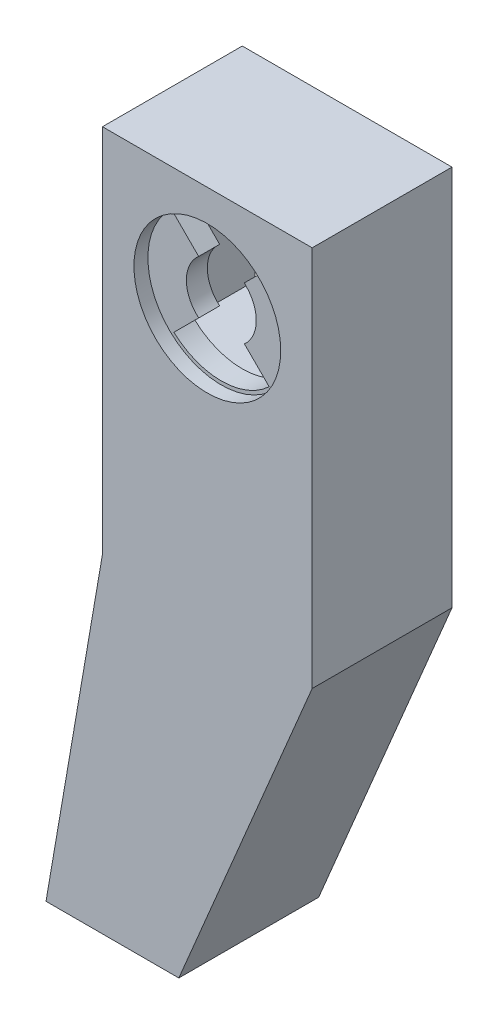
SolidWorks part; units mm, degrees
ref_plane "Front Plane" through (0, 0, 0) normal (0, 0, 1) x (1, 0, 0)
ref_plane "Top Plane" through (0, 0, 0) normal (0, 1, 0) x (1, 0, 0)
ref_plane "Right Plane" through (0, 0, 0) normal (1, 0, 0) x (0, 0, -1)
sketch "Sketch1" plane through (0, 0, 0) normal (0, 0, 1) x (1, 0, 0)
  line L0 (-46.9143, 29.8286) -> (-46.9143, -1.8875)
  line L1 (-46.9143, -1.8875) -> (-16.9143, -1.8875)
  line L2 (-16.9143, -1.8875) -> (-16.9143, 29.8286)
  line L3 (-16.9143, 29.8286) -> (-46.9143, 29.8286)
  line L4 (-46.9143, -1.8875) -> (-46.9143, -23.1318)
  line L5 (-16.9143, -1.8875) -> (-16.9143, -24.7701)
  line L8 (-45.1143, 28.0286) -> (-18.7143, 28.0286)
  line L10 (-45.1143, 1.6286) -> (-18.7143, 1.6286)
  line L12 (-45.1143, 28.0286) -> (-45.1143, 1.6286)
  line L13 (-18.7143, 28.0286) -> (-18.7143, 1.6286)
  line L14 (-45.1143, 1.6286) -> (-18.7143, 28.0286) construction
  line L15 (-45.1143, 28.0286) -> (-18.7143, 1.6286) construction
  line L16 (-28.6057, 18.6389) -> (-25.0986, 22.1461)
  line L17 (-35.1517, 18.6389) -> (-38.6931, 22.1803)
  line L18 (-28.6057, 11.0798) -> (-25.0668, 7.5408)
  line L19 (-35.1517, 11.0182) -> (-38.6931, 7.4769)
  line L22 (-35.9908, -70.1714) -> (-54.9908, -70.1714)
  line L23 (-54.9908, -70.1714) -> (-46.9143, -23.1318)
  line L24 (-16.9143, -24.7701) -> (-35.9908, -70.1714)
  line L47 (-28.6057, 18.6389) -> (-28.3788, 18.3641)
  arc A0 (-38.6931, 7.4769) -> (-25.0668, 7.5408) centre (-31.9143, 14.8286) ccw
  arc A1 (-35.1517, 18.6389) -> (-35.1517, 11.0182) centre (-31.9143, 14.8286) ccw
  arc A2 (-25.0986, 22.1461) -> (-38.6931, 22.1803) centre (-31.9143, 14.8286) ccw
  arc A3 (-28.6057, 11.0798) -> (-28.3788, 18.3641) centre (-31.9143, 14.8286) ccw
  circle A11 centre (-31.9143, 14.8286) radius 10.5
  dimension "D6" = 13.2
  dimension "D9" = 20
  dimension "D1" = 30
  dimension "D4" = 1.8
  dimension "D5" = 1.8
  dimension "D7" = 13.2
  dimension "D8" = 26.4
extrude "Boss-Extrude8" add sketch "Sketch1<25>" against normal blind 20 separate body contours L10 L13 L8 L12 | L4 L23 L22 L24 L5 L2 L3 L0
sketch "Sketch1<25>" plane through (0, 0, 0) normal (0, 0, 1) x (1, 0, 0) same geometry as "Sketch1"
extrude "Boss-Extrude9" add sketch "Sketch1<27>" against normal blind 5 contours L8 L13 L10 L12 | A3 L47 L16 A2 L17 A1 L19 A0 L18
sketch "Sketch1<27>" plane through (0, 0, 0) normal (0, 0, 1) x (1, 0, 0) same geometry as "Sketch1"
extrude "Cut-Extrude3" cut sketch "Sketch1" against normal blind 2 contours A11
ref_plane "Plane3" through (0, -70.1714, 0) normal (0, -1, 0) x (-1, 0, 0)
sketch "Sketch4" plane through (0, -70.1714, 0) normal (0, -1, 0) x (-1, 0, 0)
  line L2 (35.9908, 20) -> (54.9908, 20) construction
  line L3 (35.9908, 20) -> (35.9908, 0) construction
  circle A0 centre (40.9908, 12) radius 1.4
  circle A1 centre (49.9908, 12) radius 1.4
  dimension "D1" = 2.8
  dimension "D2" = 2.8
  dimension "D3" = 9
  dimension "D4" = 8
  dimension "D5" = 8
  dimension "D6" = 5
extrude "Cut-Extrude4" cut sketch "Sketch4" against normal blind 15
